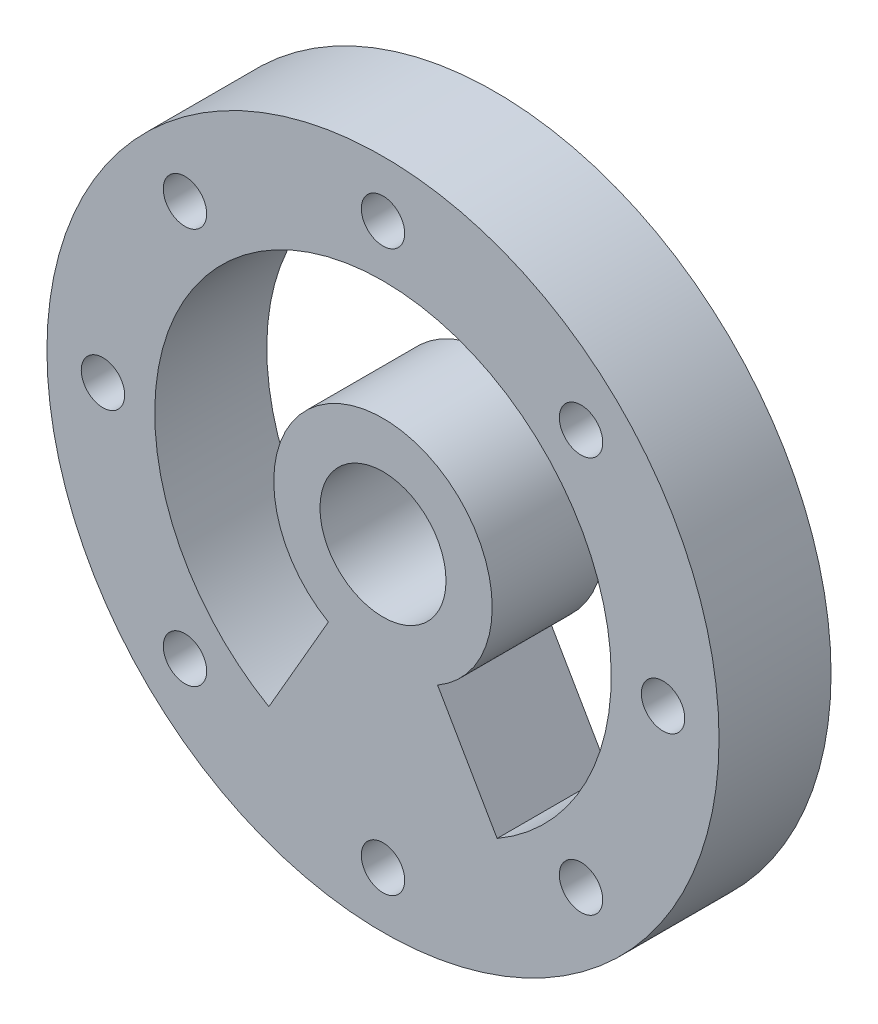
SolidWorks part; units mm, degrees
ref_plane "Front Plane" through (0, 0, 0) normal (0, 0, 1) x (1, 0, 0)
ref_plane "Top Plane" through (0, 0, 0) normal (0, 1, 0) x (1, 0, 0)
ref_plane "Right Plane" through (0, 0, 0) normal (1, 0, 0) x (0, 0, -1)
ref_axis "Axis1" through (0, 0, 5.5) along (0, 0, -1)
sketch "Sketch4" plane through (0, 0, 0) normal (0, 0, 1) x (1, 0, 0)
  line L0 (0, 0) -> (-9.5, -16.4545) construction
  line L1 (0, 0) -> (9.5, -16.4545) construction
  line L2 (-3.9, -6.755) -> (-8.15, -14.1162)
  line L3 (3.9, -6.755) -> (8.15, -14.1162)
  arc A1 (8.15, -14.1162) -> (-8.15, -14.1162) centre (0, 0) ccw
  arc A2 (3.9, -6.755) -> (-3.9, -6.755) centre (0, 0) ccw
sketch "Sketch6" plane through (0, 0, 0) normal (0, 0, 1) x (1, 0, 0)
  circle A0 centre (0, 0) radius 24
extrude "Boss-Extrude1" add sketch "Sketch6" along normal blind 8
extrude "Cut-Extrude4" cut sketch "Sketch4" along normal blind 8
sketch "Sketch7" plane through (0, 0, 0) normal (0, 0, -1) x (-1, 0, 0)
  circle A0 centre (0, 0) radius 4.5
extrude "Cut-Extrude5" cut sketch "Sketch7" against normal up to surface (8 mm away) up to face at (24, 0, 8)
sketch "Sketch8" plane through (0, 0, 0) normal (0, 0, -1) x (-1, 0, 0)
  line L0 (0, 0) -> (0, 20) construction
  circle A0 centre (0, 20) radius 1.55
  circle A1 centre (14.1421, 14.1421) radius 1.55
  circle A2 centre (20, 0) radius 1.55
  circle A3 centre (14.1421, -14.1421) radius 1.55
  circle A4 centre (0, -20) radius 1.55
  circle A5 centre (-14.1421, -14.1421) radius 1.55
  circle A6 centre (-20, 0) radius 1.55
  circle A7 centre (-14.1421, 14.1421) radius 1.55
  point P20 (0, 0)
  dimension "D1" = 8
extrude "Cut-Extrude6" cut sketch "Sketch8" against normal up to surface (8 mm away) up to face at (4.5, 0, 8)
